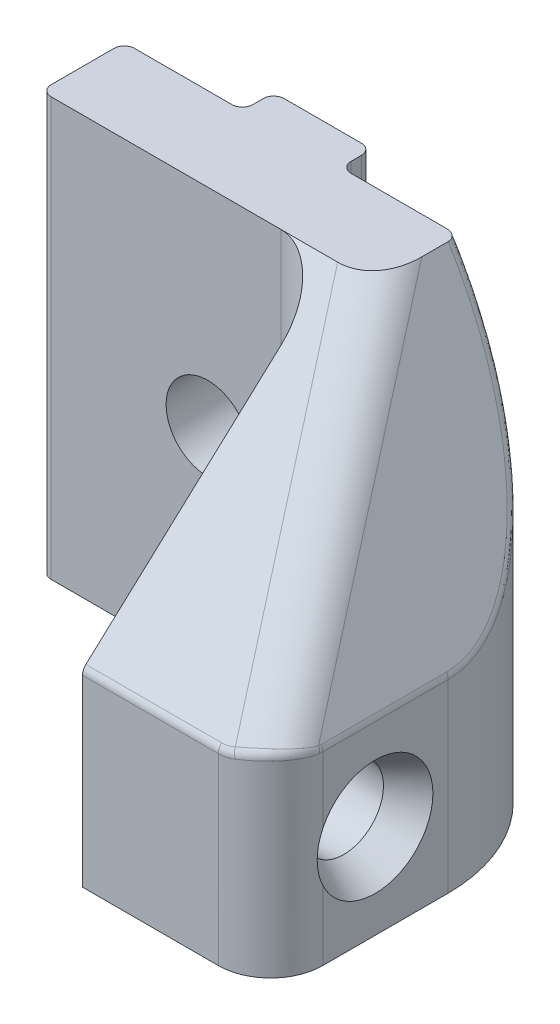
SolidWorks part; units mm, degrees
material "ABS"
ref_plane "Plan de face" through (0, 0, 0) normal (0, 0, 1) x (1, 0, 0)
ref_plane "Plan de dessus" through (0, 0, 0) normal (0, 1, 0) x (1, 0, 0)
ref_plane "Plan de droite" through (0, 0, 0) normal (1, 0, 0) x (0, 0, -1)
sketch "Esquisse1" plane through (0, 0, 0) normal (0, 1, 0) x (1, 0, 0)
  line L0 (2.35, 0) -> (15, 0)
  line L1 (-2.35, 1.5) -> (2.35, 1.5)
  line L2 (-2.35, 1.5) -> (-2.35, 0)
  line L3 (-2.35, 0) -> (2.35, 0) construction
  line L4 (2.35, 1.5) -> (2.35, 0)
  line L5 (-8, 0) -> (-2.35, 0)
  line L6 (-8, 0) -> (-8, -4)
  line L7 (-8, -4) -> (6, -4)
  line L8 (6, -4) -> (6, -16)
  line L9 (6, -16) -> (15, -16)
  line L10 (15, -16) -> (15, 0)
  dimension "D1" = 8
  dimension "D2" = 6
  dimension "D3" = 9
  dimension "D4" = 4.7
  dimension "D5" = 1.5
  dimension "D6" = 16
  dimension "D9" = 4
extrude "Boss.-Extru.1" add sketch "Esquisse1" along normal mid plane 20
sketch "Esquisse2" plane through (-1.3724, 0, 0) normal (0, 0, 1) x (1, 0, 0)
  line L0 (9.3724, 10) -> (16.3724, -1)
  line L1 (7.3724, 10) -> (16.3724, 10) construction
  line L2 (16.3724, -1) -> (16.3724, 10)
  line L3 (16.3724, 10) -> (9.3724, 10)
  line L4 (7.3724, -10) -> (16.3724, -10) construction
  line L5 (7.3724, 10) -> (7.3724, -10) construction
  circle A0 centre (1.3724, 0) radius 2
  dimension "D1" = 4
  dimension "D2" = 9
  dimension "D3" = 2
extrude "Enlèv. mat.-Extru.1" cut sketch "Esquisse2" against normal through all both and the other way through all
sketch "Esquisse3" plane through (6, 0, 0) normal (-1, 0, 0) x (0, 0, 1)
  line L0 (4, -10) -> (16, -10) construction
  line L1 (16, 10) -> (16, -1)
  line L2 (16, 10) -> (16, -10) construction
  line L3 (16, -1) -> (4, 10)
  line L4 (4, 10) -> (16, 10)
  circle A0 centre (11, -5.5) radius 1.55
  dimension "D1" = 4.5
  dimension "D3" = 5
  dimension "D4" = 3.1
  dimension "D2" = 9
extrude "Enlèv. mat.-Extru.2" cut sketch "Esquisse3" against normal through all
sketch "Esquisse4" plane through (6, 0, 0) normal (-1, 0, 0) x (0, 0, 1)
  circle A0 centre (11, -5.5) radius 1.9
  circle A1 centre (11, -5.5) radius 1.55 construction
  dimension "D1" = 3.8
extrude "Enlèv. mat.-Extru.3" cut sketch "Esquisse4" against normal through all from offset 4 offset against normal yes
chamfer "Chanfrein1" distance 1.5 angle 30 1 edges at (15, -5.5, 12.9) first distance on face at (15, -5.5, 12.9)
fillet "Congé1" radius 0.5 6 edges at (-8, 0, 4) (-8, 0, 0) (2.35, 0, 0) (2.35, 0, -1.5) (-2.35, 0, -1.5) (-2.35, 0, 0)
fillet "Congé2" radius 2.5 3 edges at (11.5, 4.5, 10) (15, -5.5, 16) (6, 0, 4)
fillet "Congé3" radius 7.5 1 edges at (15, -5.5, 0)
fillet "Congé4" radius 0.5 6 edges at (12.9772, 2.1786, 2.3765) (15, -1, 10.5) (14.997, -0.9953, 13.6222) (14.2922, -0.7795, 15.243) (12.832, -0.9797, 15.9779) (9.25, -1, 16)
